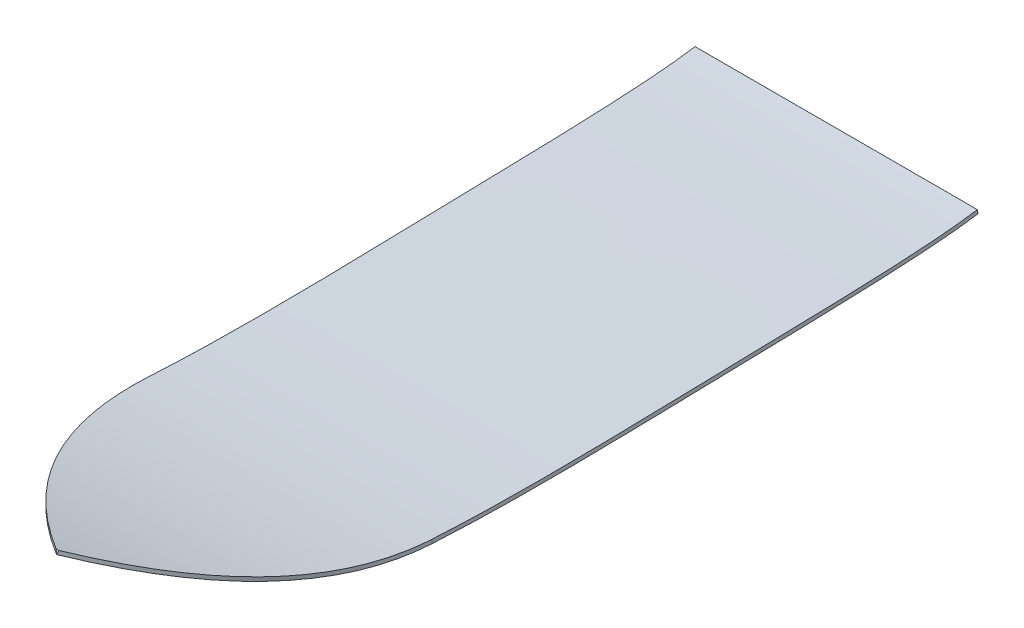
SolidWorks part; units mm, degrees
ref_plane "Front Plane" through (0, 0, 0) normal (0, 0, 1) x (1, 0, 0)
ref_plane "Top Plane" through (0, 0, 0) normal (0, 1, 0) x (1, 0, 0)
ref_plane "Right Plane" through (0, 0, 0) normal (1, 0, 0) x (0, 0, -1)
sketch "Sketch1" plane through (0, 0, 0) normal (1, 0, 0) x (0, 0, -1)
  line L22 (-3444.3151, 11.4989) -> (-3451.1384, -12.5519)
  line L23 (1519.1791, -142.9835) -> (1523.1978, -167.6584)
  spline S0 degree 3 poles (-3444.3151, 11.4989) (-3382.3836, -6.0713) (-3252.9225, -40.4712) (-3090.4493, -77.758) (-2958.3929, -104.5956) (-2828.0357, -128.8965) (-2669.014, -154.6862) (-2486.1265, -179.1057) (-2297.4931, -199.548) (-2167.5995, -210.4168) (-2088.5155, -216.0836) (-2052.5136, -218.5834) (-2020.2837, -220.6621) (-1943.6168, -225.2959) (-1840.0961, -230.6523) (-1693.3813, -236.1808) (-1549.3939, -239.844) (-1407.2154, -241.9516) (-1219.0196, -243.0192) (-984.6231, -241.6108) (-747.2737, -237.6381) (-553.2217, -233.4465) (-404.9507, -229.9155) (-253.2398, -226.1171) (-123.2806, -222.8312) (-16.7618, -220.1931) (64.621, -218.2318) (201.3808, -215.01) (367.4701, -211.1113) (559.9154, -205.9984) (722.0102, -200.9801) (931.6726, -193.1076) (1225.5902, -177.8815) (1424.9958, -158.3228) (1519.1791, -142.9835) knots 0.002322 0.002322 0.002322 0.002322 0.03125 0.0625 0.078125 0.09375 0.125 0.15625 0.1875 0.226562 0.230469 0.234375 0.248047 0.25 0.28125 0.3125 0.34375 0.375 0.40625 0.46875 0.53125 0.5625 0.59375 0.625 0.65625 0.671875 0.6875 0.703125 0.75 0.78125 0.8125 0.84375 0.90625 1 1 1 1
  spline S1 degree 1 poles (-3451.1384, -12.5519) (1523.1978, -167.6584) knots 0 0 1 1 construction
  spline S2 degree 3 poles (-3451.1384, -12.5519) (-3417.6391, -22.0558) (-3350.4034, -40.4781) (-3249.4628, -66.2155) (-3148.7644, -90.0103) (-3015.3451, -119.1388) (-2851.1037, -150.6671) (-2660.4837, -181.1984) (-2477.9137, -205.264) (-2333.1299, -220.7466) (-2221.783, -230.8773) (-2140.4688, -237.4547) (-2061.3456, -243.1205) (-1984.2772, -247.9757) (-1908.446, -252.1476) (-1808.8494, -256.8795) (-1686.7382, -261.3976) (-1542.9128, -264.9752) (-1400.8848, -267.0141) (-1259.8858, -267.7604) (-1119.2271, -267.421) (-978.3016, -266.1587) (-836.4991, -264.136) (-693.2219, -261.483) (-547.873, -258.3303) (-399.8074, -254.7964) (-273.568, -251.6332) (-170.4657, -249.0326) (-91.9788, -247.0628) (-12.2136, -245.0895) (69.0148, -243.1345) (150.8953, -241.2067) (260.7361, -238.6227) (398.6662, -235.2956) (563.2876, -230.912) (725.0819, -225.8896) (882.0823, -219.9787) (1007.2695, -214.1013) (1103.0337, -208.6999) (1172.4163, -204.2666) (1239.1112, -199.4183) (1302.8754, -194.1222) (1353.3697, -189.3076) (1392.0611, -185.1978) (1420.1985, -181.9819) (1447.4259, -178.6277) (1469.3336, -175.7132) (1486.3762, -173.3075) (1498.9147, -171.4652) (1509.152, -169.8987) (1517.2261, -168.6242) (1521.2027, -167.9833) (1523.1978, -167.6584) knots 0.002322 0.002322 0.002322 0.002322 0.01791 0.033499 0.049088 0.064677 0.095854 0.127032 0.158209 0.189386 0.204975 0.220564 0.236153 0.251741 0.26733 0.282919 0.314096 0.345274 0.376451 0.407629 0.438806 0.469983 0.501161 0.532338 0.563516 0.594693 0.625871 0.641459 0.657048 0.672637 0.688226 0.703814 0.719403 0.75058 0.781758 0.812935 0.844113 0.87529 0.890879 0.906468 0.922056 0.937645 0.953234 0.961028 0.968823 0.976617 0.984411 0.988308 0.992206 0.996103 0.998051 1 1 1 1
  dimension "D1" = 25
extrude "Boss-Extrude1" add sketch "Sketch1" along normal blind 1524 and the other way blind 1524
sketch "Sketch3" plane through (0, 0, 0) normal (0, 1, 0) x (1, 0, 0)
  line L0 (-900, 1559.398) -> (900, 1559.398)
  line L1 (-900, 1559.398) -> (-900, -1958.1357)
  line L2 (900, 1559.398) -> (900, -1958.1357)
  line L3 (0, 2955.5244) -> (0, -2061.9995) construction
  line L4 (-2934.2017, 4389.6594) -> (2797.2556, 4389.6594)
  line L5 (-2934.2017, 4389.6594) -> (-2934.2017, -3613.6465)
  line L6 (-2934.2017, -3613.6465) -> (2797.2556, -3613.6465)
  line L7 (2797.2556, 4389.6594) -> (2797.2556, -3613.6465)
  line L8 (-94.9374, 0) -> (0, 0) construction
  line L10 (-1524, -3451.1384) -> (1524, -3451.1384) construction
  line L11 (-1524, 1954.9582) -> (1524, 1954.9582) construction
  spline S0 degree 2 poles (-900, -1958.1357) (-900, -2832.7743) (0, -3451.1384) knots 0 0 0 1 1 1
  spline S1 degree 2 poles (900, -1958.1357) (900, -2832.7743) (0, -3451.1384) knots 0 0 0 1 1 1
  point P13 (0, -3451.1384)
  dimension "D1" = 1800
extrude "Cut-Extrude1" cut sketch "Sketch3" against normal through all both and the other way through all
